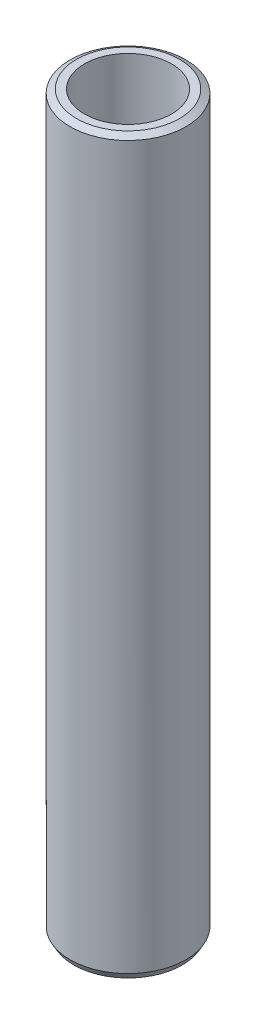
SolidWorks part; units mm, degrees
ref_plane "Front Plane" through (0, 0, 0) normal (0, 0, 1) x (1, 0, 0)
ref_plane "Top Plane" through (0, 0, 0) normal (0, 1, 0) x (1, 0, 0)
ref_plane "Right Plane" through (0, 0, 0) normal (1, 0, 0) x (0, 0, -1)
sketch "Sketch1" plane through (0, 0, 0) normal (0, 1, 0) x (1, 0, 0)
  circle A0 centre (0, 0) radius 47.5
  dimension "SHAFT_OD" = 95
extrude "Boss-Extrude1" add sketch "Sketch1" along normal blind 600
sketch "Sketch2" plane through (0, 0, 0) normal (0, 1, 0) x (1, 0, 0)
  circle A0 centre (0, 0) radius 35.6935
  dimension "BORE_D" = 71.387
extrude "Cut-Extrude1" cut sketch "Sketch2" along normal through all
chamfer "Chamfer1" distance 3.0621 angle 60 2 edges at (0, 600, 47.5) (0, 0, 47.5) first distance on face at (0, 600, 47.5) first distance on face at (0, 0, 35.6935)
